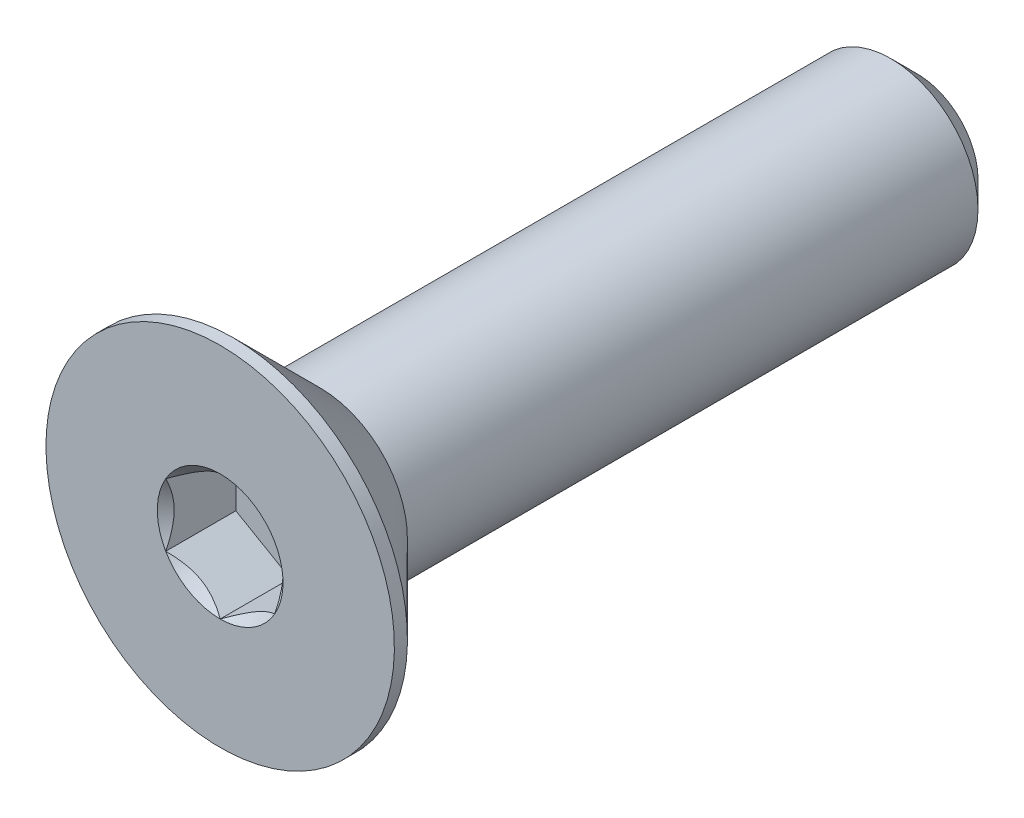
SolidWorks part; units mm, degrees
material "Alloy Steel"
ref_plane "Front" through (0, 0, 0) normal (0, 0, 1) x (1, 0, 0)
ref_plane "Top" through (0, 0, 0) normal (0, 1, 0) x (1, 0, 0)
ref_plane "Right" through (0, 0, 0) normal (1, 0, 0) x (0, 0, -1)
sketch "Sketch1" plane through (0, 0, 0) normal (1, 0, 0) x (0, 0, -1)
  line L0 (-8, 4) -> (-7.7, 4) construction
  line L1 (-7.7, 4) -> (-5.7, 2) construction
  line L2 (-8, 2) -> (8, 2) construction
  line L3 (8, 2) -> (8, 0) construction
  line L4 (8, 0) -> (-8, 0) construction
  line L5 (-8, 0) -> (-8, 4) construction
  line L6 (-8, 4) -> (-8, -4) construction
  line L7 (8, 2) -> (8, -2) construction
  line L8 (-8, -4) -> (-7.7, -4) construction
  line L9 (-7.7, -4) -> (-5.7, -2) construction
  line L11 (-8, 2) -> (-8, 0) construction
  line L12 (-5.7, 2) -> (-5.7, 0) construction
  line L13 (7.9562, 2.0758) -> (8.3063, 1.4696) construction
  line L14 (8.3063, 1.4696) -> (8.6562, 2.0758) construction
  line L15 (8.6562, 2.0758) -> (7.9562, 2.0758) construction
  line L16 (8.3063, 2.0758) -> (8.3063, 2) construction
  line L17 (8.3063, 2) -> (8.3063, 1.5453) construction
  line L18 (8.3063, 1.5453) -> (8.3063, 1.4696) construction
  line L19 (8.3063, 2.0379) -> (8.6344, 2.0379) construction
  line L20 (8.3063, 2.0379) -> (7.9781, 2.0379) construction
  line L21 (8, 2) -> (8.6125, 2) construction
  line L22 (8.2625, 1.5453) -> (8.35, 1.5453) construction
  line L23 (8, -2) -> (-5.7, -2) construction
  point P10 (6.25, -2)
  point P24 (-5.7, 2)
  point P30 (0, 0)
  dimension "Head Diameter" = 8
  dimension "Head Height" = 2.3
  dimension "Length" = 16
  dimension "Countersink Angle" = 90
  dimension "Thread Pitch" = 0.7
  dimension "D2" = 0.0875
  dimension "Minimum Thread Length" = 13.7
  dimension "Thread Size" = 4
  dimension "D1" = 1.75
sketch "Sketch2" plane through (0, 0, 0) normal (0, 0, 1) x (1, 0, 0)
  line L1 (0, 1.4434) -> (-1.25, 0.7217) construction
  line L2 (-1.25, 0.7217) -> (-1.25, -0.7217) construction
  line L3 (-1.25, -0.7217) -> (0, -1.4434) construction
  line L4 (0, -1.4434) -> (1.25, -0.7217) construction
  line L5 (1.25, -0.7217) -> (1.25, 0.7217) construction
  line L6 (1.25, 0.7217) -> (0, 1.4434) construction
  circle A0 centre (0, 0) radius 1.25 construction
  dimension "Drive Size" = 2.5
sketch "Sketch3" plane through (0, 0, 0) normal (1, 0, 0) x (0, 0, -1)
  line L0 (-8, 2) -> (8, 2)
  line L1 (8, 2) -> (8, 0)
  line L2 (8, 0) -> (-8, 0)
  line L3 (-8, 0) -> (-8, 2)
revolve "Revolve1" add sketch "Sketch3" angle 360 about L4
chamfer "Chamfer1" distance 0.6 angle 45 1 edges at (0, 2, -8)
sketch "Sketch6" plane through (0, 0, 0) normal (1, 0, 0) x (0, 0, -1)
  line L0 (-8, 4) -> (-7.7, 4)
  line L1 (-7.7, 4) -> (-5.7, 2)
  line L2 (-5.7, 2) -> (-5.7, 0)
  line L3 (-5.7, 0) -> (-8, 0)
  line L4 (-8, 0) -> (-8, 4)
revolve "Revolve2" add sketch "Sketch6" angle 360 about L4
sketch "Sketch8" plane through (0, 0, 8) normal (0, 0, 1) x (1, 0, 0)
  line L0 (0, 1.4434) -> (-1.25, 0.7217) construction
  line L1 (1.25, 0.7217) -> (0, 1.4434) construction
  line L2 (1.25, -0.7217) -> (1.25, 0.7217) construction
  line L3 (0, -1.4434) -> (1.25, -0.7217) construction
  line L4 (-1.25, 0.7217) -> (-1.25, -0.7217) construction
  line L5 (-1.25, -0.7217) -> (0, -1.4434) construction
  line L6 (0, 1.4434) -> (-1.25, 0.7217)
  line L7 (1.25, 0.7217) -> (0, 1.4434)
  line L8 (1.25, -0.7217) -> (1.25, 0.7217)
  line L9 (0, -1.4434) -> (1.25, -0.7217)
  line L10 (-1.25, 0.7217) -> (-1.25, -0.7217)
  line L11 (-1.25, -0.7217) -> (0, -1.4434)
extrude "Cut-Extrude1" cut sketch "Sketch8" against normal blind 1.61
sketch "Sketch9" plane through (0, 0, 8) normal (0, 0, 1) x (1, 0, 0)
  circle A0 centre (0, 0) radius 1.4434
extrude "Cut-Extrude2" cut sketch "Sketch9" against normal up to next (1.61 mm away) draft 45
ref_plane "Plane1" [suppressed] through (0, 0, 5.7) normal (0, 0, 1) x (1, 0, 0)
split "Split1" [suppressed] bodies to split 124
sketch "Sketch4" [suppressed] plane through (0, 0, -8) normal (0, 0, -1) x (-1, 0, 0)
  circle A0 centre (0, 0) radius 2 construction
  circle A1 centre (0, 0) radius 2
curve "Helix/Spiral1" [suppressed] pitch 0.7 height 14.4 turns 20.5714
sketch "Sketch10" [suppressed] plane through (0, 0, 0) normal (1, 0, 0) x (0, 0, -1)
  line L0 (7.9781, 2.0379) -> (8.6344, 2.0379)
  line L1 (8.6344, 2.0379) -> (8.35, 1.5453)
  line L2 (8.35, 1.5453) -> (8.2625, 1.5453)
  line L3 (8.2625, 1.5453) -> (7.9781, 2.0379)
sweep "Cut-Sweep1" [suppressed] cut profiles "Sketch10" path "Helix/Spiral1"
equation "\"D2@Sketch1\" = \"Thread Pitch@Sketch1\" / 8"
equation "\"D4@Helix/Spiral1\"=\"Thread Pitch@Sketch1\""
equation "\"D3@Helix/Spiral1\"=\"Minimum Thread Length@Sketch1\"+\"Thread Pitch@Sketch1\""
equation "\"D1@Chamfer1\"=\"Thread Size@Sketch1\"*.15"
equation "\"D1@Cut-Extrude1\"=\"Head Height@Sketch1\"*.7"
equation "\"D1@Sketch1\"=\"Thread Pitch@Sketch1\"*2.5"
